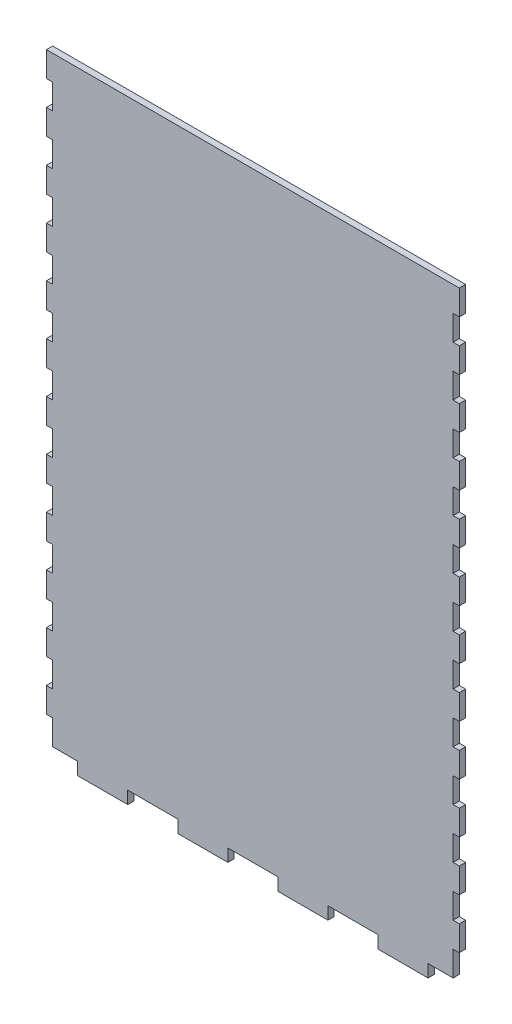
SolidWorks part; units mm, degrees
ref_plane "Front Plane" through (0, 0, 0) normal (0, 0, 1) x (1, 0, 0)
ref_plane "Top Plane" through (0, 0, 0) normal (0, 1, 0) x (1, 0, 0)
ref_plane "Right Plane" through (0, 0, 0) normal (1, 0, 0) x (0, 0, -1)
sketch "Sketch1" plane through (0, 0, 0) normal (0, 0, 1) x (1, 0, 0)
  line L0 (0, 0) -> (203.2, 0)
  line L1 (203.2, 0) -> (203.2, 304.8)
  line L2 (203.2, 304.8) -> (0, 304.8)
  line L3 (0, 304.8) -> (0, 0)
  dimension "D1" = 203.2
  dimension "D2" = 304.8
extrude "Boss-Extrude1" add sketch "Sketch1" along normal blind 3.175
sketch "Sketch2" plane through (0, 0, 3.175) normal (0, 0, 1) x (1, 0, 0)
  line L0 (0, 304.8) -> (-3.175, 304.8)
  line L1 (-3.175, 304.8) -> (-3.175, 292.1)
  line L2 (-3.175, 292.1) -> (0, 292.1)
  line L3 (0, 304.8) -> (0, 0) construction
  line L4 (0, 292.1) -> (0, 304.8)
  line L5 (101.6, 304.8) -> (101.6, 0) construction
  line L6 (203.2, 304.8) -> (0, 304.8) construction
  line L7 (0, 0) -> (203.2, 0) construction
  line L8 (206.375, 292.1) -> (203.2, 292.1)
  line L9 (206.375, 304.8) -> (206.375, 292.1)
  line L10 (203.2, 304.8) -> (206.375, 304.8)
  line L11 (203.2, 292.1) -> (203.2, 304.8)
  line L12 (0, 266.7) -> (0, 279.4)
  line L13 (0, 279.4) -> (-3.175, 279.4)
  line L14 (-3.175, 279.4) -> (-3.175, 266.7)
  line L15 (-3.175, 266.7) -> (0, 266.7)
  line L16 (206.375, 266.7) -> (203.2, 266.7)
  line L17 (203.2, 266.7) -> (203.2, 279.4)
  line L18 (203.2, 279.4) -> (206.375, 279.4)
  line L19 (206.375, 279.4) -> (206.375, 266.7)
  line L20 (0, 241.3) -> (0, 254)
  line L21 (0, 254) -> (-3.175, 254)
  line L22 (-3.175, 254) -> (-3.175, 241.3)
  line L23 (-3.175, 241.3) -> (0, 241.3)
  line L24 (206.375, 241.3) -> (203.2, 241.3)
  line L25 (203.2, 241.3) -> (203.2, 254)
  line L26 (203.2, 254) -> (206.375, 254)
  line L27 (206.375, 254) -> (206.375, 241.3)
  line L28 (0, 215.9) -> (0, 228.6)
  line L29 (0, 228.6) -> (-3.175, 228.6)
  line L30 (-3.175, 228.6) -> (-3.175, 215.9)
  line L31 (-3.175, 215.9) -> (0, 215.9)
  line L32 (206.375, 215.9) -> (203.2, 215.9)
  line L33 (203.2, 215.9) -> (203.2, 228.6)
  line L34 (203.2, 228.6) -> (206.375, 228.6)
  line L35 (206.375, 228.6) -> (206.375, 215.9)
  line L36 (0, 190.5) -> (0, 203.2)
  line L37 (0, 203.2) -> (-3.175, 203.2)
  line L38 (-3.175, 203.2) -> (-3.175, 190.5)
  line L39 (-3.175, 190.5) -> (0, 190.5)
  line L40 (206.375, 190.5) -> (203.2, 190.5)
  line L41 (203.2, 190.5) -> (203.2, 203.2)
  line L42 (203.2, 203.2) -> (206.375, 203.2)
  line L43 (206.375, 203.2) -> (206.375, 190.5)
  line L44 (0, 165.1) -> (0, 177.8)
  line L45 (0, 177.8) -> (-3.175, 177.8)
  line L46 (-3.175, 177.8) -> (-3.175, 165.1)
  line L47 (-3.175, 165.1) -> (0, 165.1)
  line L48 (206.375, 165.1) -> (203.2, 165.1)
  line L49 (203.2, 165.1) -> (203.2, 177.8)
  line L50 (203.2, 177.8) -> (206.375, 177.8)
  line L51 (206.375, 177.8) -> (206.375, 165.1)
  line L52 (0, 139.7) -> (0, 152.4)
  line L53 (0, 152.4) -> (-3.175, 152.4)
  line L54 (-3.175, 152.4) -> (-3.175, 139.7)
  line L55 (-3.175, 139.7) -> (0, 139.7)
  line L56 (206.375, 139.7) -> (203.2, 139.7)
  line L57 (203.2, 139.7) -> (203.2, 152.4)
  line L58 (203.2, 152.4) -> (206.375, 152.4)
  line L59 (206.375, 152.4) -> (206.375, 139.7)
  line L60 (0, 114.3) -> (0, 127)
  line L61 (0, 127) -> (-3.175, 127)
  line L62 (-3.175, 127) -> (-3.175, 114.3)
  line L63 (-3.175, 114.3) -> (0, 114.3)
  line L64 (206.375, 114.3) -> (203.2, 114.3)
  line L65 (203.2, 114.3) -> (203.2, 127)
  line L66 (203.2, 127) -> (206.375, 127)
  line L67 (206.375, 127) -> (206.375, 114.3)
  line L68 (0, 88.9) -> (0, 101.6)
  line L69 (0, 101.6) -> (-3.175, 101.6)
  line L70 (-3.175, 101.6) -> (-3.175, 88.9)
  line L71 (-3.175, 88.9) -> (0, 88.9)
  line L72 (206.375, 88.9) -> (203.2, 88.9)
  line L73 (203.2, 88.9) -> (203.2, 101.6)
  line L74 (203.2, 101.6) -> (206.375, 101.6)
  line L75 (206.375, 101.6) -> (206.375, 88.9)
  line L76 (0, 63.5) -> (0, 76.2)
  line L77 (0, 76.2) -> (-3.175, 76.2)
  line L78 (-3.175, 76.2) -> (-3.175, 63.5)
  line L79 (-3.175, 63.5) -> (0, 63.5)
  line L80 (206.375, 63.5) -> (203.2, 63.5)
  line L81 (203.2, 63.5) -> (203.2, 76.2)
  line L82 (203.2, 76.2) -> (206.375, 76.2)
  line L83 (206.375, 76.2) -> (206.375, 63.5)
  line L84 (0, 38.1) -> (0, 50.8)
  line L85 (0, 50.8) -> (-3.175, 50.8)
  line L86 (-3.175, 50.8) -> (-3.175, 38.1)
  line L87 (-3.175, 38.1) -> (0, 38.1)
  line L88 (206.375, 38.1) -> (203.2, 38.1)
  line L89 (203.2, 38.1) -> (203.2, 50.8)
  line L90 (203.2, 50.8) -> (206.375, 50.8)
  line L91 (206.375, 50.8) -> (206.375, 38.1)
  line L92 (0, 12.7) -> (0, 25.4)
  line L93 (0, 25.4) -> (-3.175, 25.4)
  line L94 (-3.175, 25.4) -> (-3.175, 12.7)
  line L95 (-3.175, 12.7) -> (0, 12.7)
  line L96 (206.375, 12.7) -> (203.2, 12.7)
  line L97 (203.2, 12.7) -> (203.2, 25.4)
  line L98 (203.2, 25.4) -> (206.375, 25.4)
  line L99 (206.375, 25.4) -> (206.375, 12.7)
  line L100 (0, 292.1) -> (0, 266.7) construction
  line L101 (12.7, 0) -> (12.7, -6.35)
  line L102 (12.7, -6.35) -> (38.1, -6.35)
  line L103 (38.1, -6.35) -> (38.1, 0)
  line L104 (38.1, 0) -> (12.7, 0)
  line L105 (88.9, 0) -> (63.5, 0)
  line L106 (63.5, 0) -> (63.5, -6.35)
  line L107 (63.5, -6.35) -> (88.9, -6.35)
  line L108 (88.9, -6.35) -> (88.9, 0)
  line L109 (139.7, 0) -> (114.3, 0)
  line L110 (114.3, 0) -> (114.3, -6.35)
  line L111 (114.3, -6.35) -> (139.7, -6.35)
  line L112 (139.7, -6.35) -> (139.7, 0)
  line L113 (190.5, 0) -> (165.1, 0)
  line L114 (165.1, 0) -> (165.1, -6.35)
  line L115 (165.1, -6.35) -> (190.5, -6.35)
  line L116 (190.5, -6.35) -> (190.5, 0)
  line L117 (38.1, 0) -> (88.9, 0) construction
  dimension "D1" = 3.175
  dimension "D2" = 12.7
  dimension "D4" = 25.4
  dimension "D5" = 12.7
  dimension "D6" = 6.35
  dimension "D7" = 25.4
  dimension "D9" = 50.8
  dimension "D3" = 12
  dimension "D8" = 4
extrude "Boss-Extrude2" add sketch "Sketch2" against normal up to surface (3.175 mm away) up to face at (101.6, 152.4, 0)
sketch "Sketch3" [suppressed] plane through (0, 0, 3.175) normal (0, 0, 1) x (1, 0, 0)
  line L0 (0, 0) -> (-3.175, 0)
  line L1 (-3.175, 0) -> (-3.175, 12.7)
  line L2 (-3.175, 12.7) -> (0, 12.7)
  line L3 (0, 304.8) -> (0, 0) construction
  line L4 (0, 12.7) -> (0, 0)
  line L5 (101.6, 304.8) -> (101.6, 0) construction
  line L6 (203.2, 304.8) -> (0, 304.8) construction
  line L7 (0, 0) -> (203.2, 0) construction
  line L8 (206.375, 12.7) -> (203.2, 12.7)
  line L9 (206.375, 0) -> (206.375, 12.7)
  line L10 (203.2, 0) -> (206.375, 0)
  line L11 (203.2, 12.7) -> (203.2, 0)
  line L12 (0, 38.1) -> (0, 25.4)
  line L13 (0, 25.4) -> (-3.175, 25.4)
  line L14 (-3.175, 25.4) -> (-3.175, 38.1)
  line L15 (-3.175, 38.1) -> (0, 38.1)
  line L16 (206.375, 38.1) -> (203.2, 38.1)
  line L17 (203.2, 38.1) -> (203.2, 25.4)
  line L18 (203.2, 25.4) -> (206.375, 25.4)
  line L19 (206.375, 25.4) -> (206.375, 38.1)
  line L20 (0, 63.5) -> (0, 50.8)
  line L21 (0, 50.8) -> (-3.175, 50.8)
  line L22 (-3.175, 50.8) -> (-3.175, 63.5)
  line L23 (-3.175, 63.5) -> (0, 63.5)
  line L24 (206.375, 63.5) -> (203.2, 63.5)
  line L25 (203.2, 63.5) -> (203.2, 50.8)
  line L26 (203.2, 50.8) -> (206.375, 50.8)
  line L27 (206.375, 50.8) -> (206.375, 63.5)
  line L28 (0, 88.9) -> (0, 76.2)
  line L29 (0, 76.2) -> (-3.175, 76.2)
  line L30 (-3.175, 76.2) -> (-3.175, 88.9)
  line L31 (-3.175, 88.9) -> (0, 88.9)
  line L32 (206.375, 88.9) -> (203.2, 88.9)
  line L33 (203.2, 88.9) -> (203.2, 76.2)
  line L34 (203.2, 76.2) -> (206.375, 76.2)
  line L35 (206.375, 76.2) -> (206.375, 88.9)
  line L36 (0, 114.3) -> (0, 101.6)
  line L37 (0, 101.6) -> (-3.175, 101.6)
  line L38 (-3.175, 101.6) -> (-3.175, 114.3)
  line L39 (-3.175, 114.3) -> (0, 114.3)
  line L40 (206.375, 114.3) -> (203.2, 114.3)
  line L41 (203.2, 114.3) -> (203.2, 101.6)
  line L42 (203.2, 101.6) -> (206.375, 101.6)
  line L43 (206.375, 101.6) -> (206.375, 114.3)
  line L44 (0, 139.7) -> (0, 127)
  line L45 (0, 127) -> (-3.175, 127)
  line L46 (-3.175, 127) -> (-3.175, 139.7)
  line L47 (-3.175, 139.7) -> (0, 139.7)
  line L48 (206.375, 139.7) -> (203.2, 139.7)
  line L49 (203.2, 139.7) -> (203.2, 127)
  line L50 (203.2, 127) -> (206.375, 127)
  line L51 (206.375, 127) -> (206.375, 139.7)
  line L52 (0, 165.1) -> (0, 152.4)
  line L53 (0, 152.4) -> (-3.175, 152.4)
  line L54 (-3.175, 152.4) -> (-3.175, 165.1)
  line L55 (-3.175, 165.1) -> (0, 165.1)
  line L56 (206.375, 165.1) -> (203.2, 165.1)
  line L57 (203.2, 165.1) -> (203.2, 152.4)
  line L58 (203.2, 152.4) -> (206.375, 152.4)
  line L59 (206.375, 152.4) -> (206.375, 165.1)
  line L60 (0, 190.5) -> (0, 177.8)
  line L61 (0, 177.8) -> (-3.175, 177.8)
  line L62 (-3.175, 177.8) -> (-3.175, 190.5)
  line L63 (-3.175, 190.5) -> (0, 190.5)
  line L64 (206.375, 190.5) -> (203.2, 190.5)
  line L65 (203.2, 190.5) -> (203.2, 177.8)
  line L66 (203.2, 177.8) -> (206.375, 177.8)
  line L67 (206.375, 177.8) -> (206.375, 190.5)
  line L68 (0, 215.9) -> (0, 203.2)
  line L69 (0, 203.2) -> (-3.175, 203.2)
  line L70 (-3.175, 203.2) -> (-3.175, 215.9)
  line L71 (-3.175, 215.9) -> (0, 215.9)
  line L72 (206.375, 215.9) -> (203.2, 215.9)
  line L73 (203.2, 215.9) -> (203.2, 203.2)
  line L74 (203.2, 203.2) -> (206.375, 203.2)
  line L75 (206.375, 203.2) -> (206.375, 215.9)
  line L76 (0, 241.3) -> (0, 228.6)
  line L77 (0, 228.6) -> (-3.175, 228.6)
  line L78 (-3.175, 228.6) -> (-3.175, 241.3)
  line L79 (-3.175, 241.3) -> (0, 241.3)
  line L80 (206.375, 241.3) -> (203.2, 241.3)
  line L81 (203.2, 241.3) -> (203.2, 228.6)
  line L82 (203.2, 228.6) -> (206.375, 228.6)
  line L83 (206.375, 228.6) -> (206.375, 241.3)
  line L84 (0, 266.7) -> (0, 254)
  line L85 (0, 254) -> (-3.175, 254)
  line L86 (-3.175, 254) -> (-3.175, 266.7)
  line L87 (-3.175, 266.7) -> (0, 266.7)
  line L88 (206.375, 266.7) -> (203.2, 266.7)
  line L89 (203.2, 266.7) -> (203.2, 254)
  line L90 (203.2, 254) -> (206.375, 254)
  line L91 (206.375, 254) -> (206.375, 266.7)
  line L92 (0, 292.1) -> (0, 279.4)
  line L93 (0, 279.4) -> (-3.175, 279.4)
  line L94 (-3.175, 279.4) -> (-3.175, 292.1)
  line L95 (-3.175, 292.1) -> (0, 292.1)
  line L96 (206.375, 292.1) -> (203.2, 292.1)
  line L97 (203.2, 292.1) -> (203.2, 279.4)
  line L98 (203.2, 279.4) -> (206.375, 279.4)
  line L99 (206.375, 279.4) -> (206.375, 292.1)
  line L100 (0, 12.7) -> (0, 38.1) construction
  line L101 (12.7, 0) -> (12.7, -6.35)
  line L102 (12.7, -6.35) -> (38.1, -6.35)
  line L103 (38.1, -6.35) -> (38.1, 0)
  line L104 (38.1, 0) -> (12.7, 0)
  line L105 (88.9, 0) -> (63.5, 0)
  line L106 (63.5, 0) -> (63.5, -6.35)
  line L107 (63.5, -6.35) -> (88.9, -6.35)
  line L108 (88.9, -6.35) -> (88.9, 0)
  line L109 (139.7, 0) -> (114.3, 0)
  line L110 (114.3, 0) -> (114.3, -6.35)
  line L111 (114.3, -6.35) -> (139.7, -6.35)
  line L112 (139.7, -6.35) -> (139.7, 0)
  line L113 (190.5, 0) -> (165.1, 0)
  line L114 (165.1, 0) -> (165.1, -6.35)
  line L115 (165.1, -6.35) -> (190.5, -6.35)
  line L116 (190.5, -6.35) -> (190.5, 0)
  line L117 (38.1, 0) -> (88.9, 0) construction
  dimension "D1" = 3.175
  dimension "D2" = 12.7
  dimension "D4" = 25.4
  dimension "D9" = 50.8
  dimension "D3" = 12
  dimension "D8" = 4
  dimension "D5" = 6.35
  dimension "D6" = 25.4
  dimension "D7" = 12.7
extrude "Boss-Extrude3" [suppressed] add sketch "Sketch3" against normal up to surface (3.175 mm away) up to face at (101.6, 130.175, 0)
equation "\"wall_thickness\"= 0.125in"
equation "\"base_thickness\"= 0.25in"
equation "\"D1@Boss-Extrude1\"=\"wall_thickness\""
equation "\"D1@Sketch2\"=\"wall_thickness\""
equation "\"D6@Sketch2\"=\"base_thickness\""
equation "\"D1@Sketch3\"=\"wall_thickness\""
equation "\"D5@Sketch3\"=\"base_thickness\""
